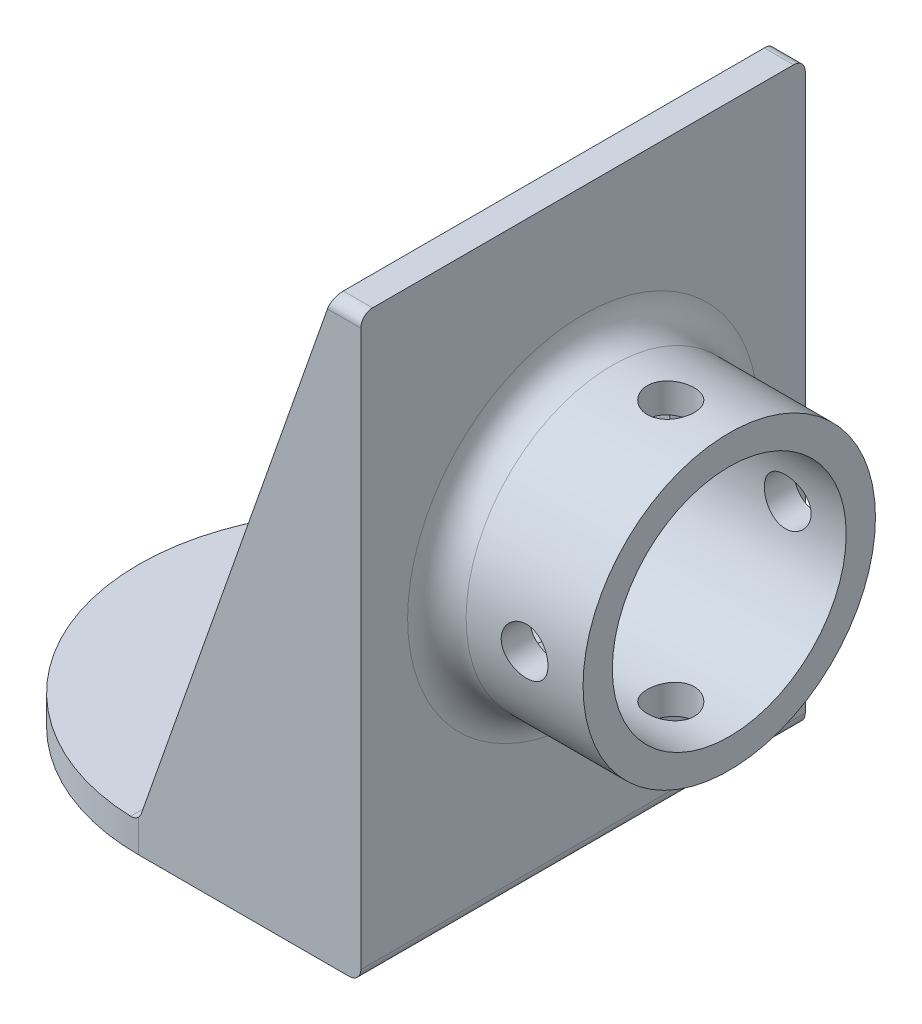
SolidWorks part; units mm, degrees
ref_plane "Спереди" through (0, 0, 0) normal (0, 0, 1) x (1, 0, 0)
ref_plane "Сверху" through (0, 0, 0) normal (0, 1, 0) x (1, 0, 0)
ref_plane "Справа" through (0, 0, 0) normal (1, 0, 0) x (0, 0, -1)
sketch "Эскиз3" plane through (0, 0, 0) normal (0, 0, 1) x (1, 0, 0)
  line L1 (76, 0) -> (0, 0)
  line L3 (71, 5) -> (0, 5)
  line L4 (0, 0) -> (0, 5)
  line L8 (76, 0) -> (76, 99)
  line L9 (76, 99) -> (71, 99)
  line L10 (71, 5) -> (71, 99)
  point P0 (0, 0)
  dimension "D1" = 5
  dimension "D2" = 76
  dimension "D3" = 5
  dimension "D4" = 99
extrude "Бобышка-Вытянуть1" add sketch "Эскиз3" along normal blind 76
fillet "Скругление1" radius 38 2 edges at (0, 2.5, 0) (0, 2.5, 76)
ref_plane "Плоскость7" through (0, 0, 0) normal (0, 0, -1) x (-1, 0, 0)
ref_plane "Плоскость8" through (0, 0, 76) normal (0, 0, 1) x (1, 0, 0)
sketch "Эскиз4" plane through (0, 0, 76) normal (0, 0, 1) x (1, 0, 0)
  line L0 (71, 99) -> (38, 5)
rib "Ребро1" sketch "Эскиз4" sketch "Эскиз4" thickness 5 extrusion direction parallel to sketch draft on no parameters "D1"=5
sketch "Эскиз5" plane through (0, 0, 0) normal (0, 0, -1) x (-1, 0, 0)
  line L0 (-71, 99) -> (-38, 5)
rib "Ребро2" sketch "Эскиз5" sketch "Эскиз5" thickness 5 extrusion direction parallel to sketch draft on no parameters "D1"=5
sketch "Эскиз7" plane through (0, 5, 0) normal (0, 1, 0) x (1, 0, 0)
  line L0 (38, -38) -> (20, -38) construction
  circle A0 centre (38, -38) radius 18 construction
  circle A1 centre (20, -38) radius 2.5
  circle A2 centre (38, -38) radius 18
  circle A3 centre (29, -22.4115) radius 2.5
  circle A4 centre (38, -38) radius 18
  circle A5 centre (47, -22.4115) radius 2.5
  circle A6 centre (38, -38) radius 18
  circle A7 centre (56, -38) radius 2.5
  circle A8 centre (38, -38) radius 18
  circle A9 centre (47, -53.5885) radius 2.5
  circle A10 centre (38, -38) radius 18
  circle A11 centre (29, -53.5885) radius 2.5
  dimension "D1" = 36
  dimension "D2" = 5
  dimension "D3" = 6
extrude "Вырез-Вытянуть1" cut sketch "Эскиз7" against normal blind 10 contours A1 | A3 | A5 | A7 | A9 | A11
sketch "Эскиз8" plane through (76, 0, 0) normal (1, 0, 0) x (0, 0, -1)
  line L2 (-76, 0) -> (0, 0) construction
  line L3 (0, 0) -> (0, 99) construction
  circle A12 centre (-38, 50) radius 25
  circle A13 centre (-38, 50) radius 20
  point P7 (-38, 75)
  dimension "D1" = 50
  dimension "D2" = 40
  dimension "D4" = 38
  dimension "D3" = 50
fillet "Скругление2" radius 2 1 edges at (76, 0, 38)
chamfer "Фаска1" distance 10 distance2 5 1 edges at (71, 5, 38) first distance on face at (71, 52, 38)
fillet "Скругление3" radius 2 2 edges at (38, 5, 73.5) (38, 5, 2.5)
fillet "Скругление4" radius 2 2 edges at (73.5, 99, 0) (73.5, 99, 76)
extrude "Вырез-Вытянуть2" cut sketch "Эскиз8" against normal blind 5 contours A13
extrude "Бобышка-Вытянуть4" add sketch "Эскиз8<6>" along normal blind 25 contours A12 | A13
sketch "Эскиз8<6>" plane through (76, 0, 0) normal (1, 0, 0) x (0, 0, -1) same geometry as "Эскиз8"
fillet "Скругление5" radius 5 1 edges at (76, 50, 63)
sketch "Эскиз13" plane through (0, 0, 0) normal (0, 0, -1) x (-1, 0, 0)
  line L0 (-101, 75) -> (-101, 25) construction
  line L1 (-101, 25) -> (-81, 25) construction
  circle A0 centre (-91, 50) radius 4
  dimension "D1" = 8
  dimension "D2" = 10
  dimension "D3" = 25
extrude "Вырез-Вытянуть3" cut sketch "Эскиз13" against normal blind 76
ref_plane "Плоскость9" through (0, 99, 0) normal (0, 1, 0) x (1, 0, 0)
sketch "Эскиз14" plane through (0, 99, 0) normal (0, 1, 0) x (1, 0, 0)
  line L0 (101, -63) -> (101, -13) construction
  line L1 (95, -63) -> (101, -63) construction
  circle A0 centre (91, -38) radius 4
  dimension "D1" = 8
  dimension "D2" = 10
  dimension "D3" = 25
extrude "Вырез-Вытянуть4" cut sketch "Эскиз14" against normal blind 76
